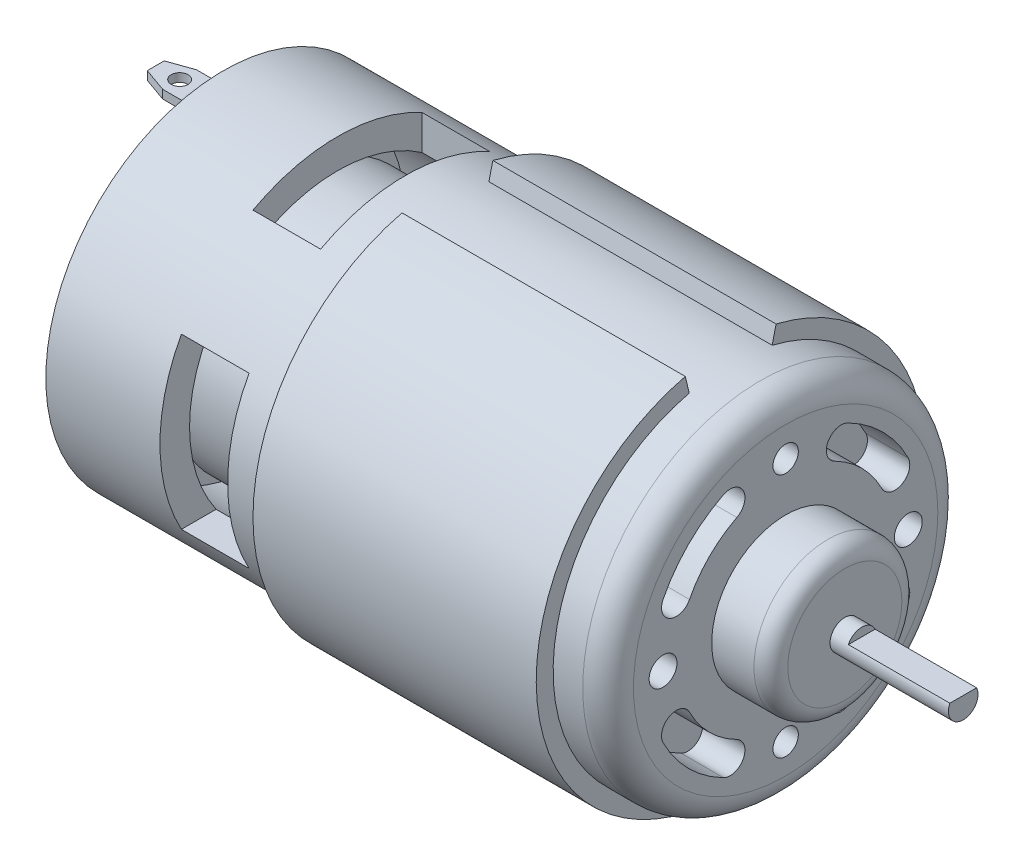
SolidWorks part; units mm, degrees
material "1060 Alloy"
ref_plane "Front Plane" through (0, 0, 0) normal (0, 0, 1) x (1, 0, 0)
ref_plane "Top Plane" through (0, 0, 0) normal (0, 1, 0) x (1, 0, 0)
ref_plane "Right Plane" through (0, 0, 0) normal (1, 0, 0) x (0, 0, -1)
sketch "Sketch1" plane through (0, 0, 0) normal (1, 0, 0) x (0, 0, -1)
  circle A0 centre (0, 0) radius 21
  dimension "D1" = 42
extrude "Boss-Extrude1" add sketch "Sketch1" along normal blind 66.5
fillet "Fillet1" radius 3 1 edges at (66.5, 0, -21)
sketch "Sketch2" plane through (66.5, 0, 0) normal (1, 0, 0) x (0, 0, -1)
  circle A0 centre (0, 0) radius 8.75
  dimension "D1" = 17.5
extrude "Boss-Extrude2" add sketch "Sketch2" along normal blind 7
fillet "Fillet2" radius 2 1 edges at (73.5, 0, -8.75)
sketch "Sketch3" plane through (73.5, 0, 0) normal (1, 0, 0) x (0, 0, -1)
  circle A0 centre (0, 0) radius 1.75
  dimension "D1" = 3.5
extrude "Boss-Extrude3" add sketch "Sketch3" along normal blind 14
ref_plane "Plane1" through (60, 0, 0) normal (1, 0, 0) x (0, 0, -1)
sketch "Sketch4" plane through (60, 0, 0) normal (1, 0, 0) x (0, 0, -1)
  line L0 (-5.3694, 22.3645) -> (-4.9025, 20.4197)
  line L1 (4.9025, 20.4197) -> (5.4896, 22.8652)
  circle A0 centre (0, 0) radius 23
  circle A1 centre (0, 0) radius 21 construction
  circle A2 centre (0, 0) radius 21
  dimension "D1" = 46
  dimension "D2" = 42
extrude "Boss-Extrude4" add sketch "Sketch4" against normal blind 33.5 contours A2 L0 A0 L1 region at (60, 21.2413, 5.7642)
sketch "Sketch5" plane through (0, 0, 0) normal (-1, 0, 0) x (0, 0, 1)
  line L0 (0, 21) -> (0, -21) construction
  line L2 (-2, 17.5) -> (2, 17.5)
  line L3 (-2, 17.5) -> (-2, 16.5)
  line L4 (-2, 16.5) -> (2, 16.5)
  line L5 (2, 17.5) -> (2, 16.5)
  line L6 (-2, 17.5) -> (2, 16.5) construction
  line L7 (-2, 16.5) -> (2, 17.5) construction
  line L8 (-2, -16.5) -> (2, -16.5)
  line L9 (-2, -16.5) -> (-2, -17.5)
  line L10 (-2, -17.5) -> (2, -17.5)
  line L11 (2, -16.5) -> (2, -17.5)
  line L12 (-2, -16.5) -> (2, -17.5) construction
  line L13 (-2, -17.5) -> (2, -16.5) construction
  circle A0 centre (0, 0) radius 21 construction
  arc A1 (-4.9025, 20.4197) -> (4.9025, 20.4197) centre (0, 0) ccw construction
  circle A2 centre (0, 0) radius 19
  point P7 (0, 17)
  point P12 (0, -17)
  dimension "D5" = 2
  dimension "D1" = 34
  dimension "D2" = 17
  dimension "D3" = 4
  dimension "D4" = 1
extrude "Cut-Extrude1" cut sketch "Sketch5" against normal blind 2
extrude "Boss-Extrude5" add sketch "Sketch5<3>" along normal blind 8 contours L4 L5 L2 L3 | L8 L11 L10 L9
sketch "Sketch5<3>" plane through (0, 0, 0) normal (-1, 0, 0) x (0, 0, 1) same geometry as "Sketch5"
sketch "Sketch6" plane through (0, -17.5, 0) normal (0, -1, 0) x (1, 0, 0)
  line L0 (-5.1716, -2) -> (-8, -1)
  line L1 (2, -2) -> (-8, -2) construction
  line L2 (-8, -2) -> (-8, 2) construction
  line L3 (-8, -1) -> (-8, 1)
  line L4 (-8, 1) -> (-5.1716, 2)
  line L5 (2, 2) -> (-8, 2) construction
  line L6 (-5.1716, -2) -> (-8, -2)
  line L7 (-8, -2) -> (-8, -1)
  line L8 (-7.7692, 1.1937) -> (-8, 1)
  line L9 (-8, 1) -> (-8, 2)
  line L10 (-8, 2) -> (-5.1716, 2)
  line M7 (2, 2) -> (-8, 2)
  line M8 (-8, 2) -> (-8, -2)
  line M9 (-8, -2) -> (2, -2)
  dimension "D1" = 3
  dimension "D2" = 1
extrude "Cut-Extrude2" cut sketch "Sketch6" against normal blind 37 contours L0 M9 M8 | L4 M8 M7 region at (-7.0572, -17.5, -1.6667) region at (-7.0572, -17.5, 1.6667)
ref_plane "Plane2" through (0, 21, 0) normal (0, 1, 0) x (1, 0, 0)
sketch "Sketch7" plane through (0, 21, 0) normal (0, 1, 0) x (1, 0, 0)
  line L0 (0, 0) -> (29.2331, 0) construction
  line L1 (21.5, -21) -> (21.5, 21) construction
  line L2 (0, -21) -> (26.5, -21) construction
  line L3 (26.5, 21) -> (0, 21) construction
  line L4 (26.5, 23) -> (26.5, -23) construction
  line L6 (21.5, -10) -> (13.5, -10)
  line L7 (21.5, -10) -> (21.5, 10)
  line L8 (21.5, 10) -> (13.5, 10)
  line L9 (13.5, -10) -> (13.5, 10)
  dimension "D1" = 5
  dimension "D2" = 10
  dimension "D3" = 10
  dimension "D4" = 8
extrude "Cut-Extrude3" cut sketch "Sketch7" against normal through all
pattern_circular "CirPattern1" count 2 every 90 about axis through (0, 0, 0) along (-1, 0, 0) of "Cut-Extrude3"
sketch "Sketch9" plane through (2, 0, 0) normal (-1, 0, 0) x (0, 0, 1)
  circle A0 centre (0, 0) radius 17.5
  dimension "D1" = 35
extrude "Boss-Extrude6" add sketch "Sketch9" against normal up to surface (64.5 mm away) up to face at (66.5, 0, -8.75)
sketch "Sketch10" plane through (0, 17.5, 0) normal (0, 1, 0) x (1, 0, 0)
  line L0 (-8, 0) -> (0, 0) construction
  line L1 (-8, 1) -> (-8, -1) construction
  line L2 (-5.1716, 2) -> (-5.1716, -2) construction
  line L3 (-8, 1) -> (-5.1716, 2) construction
  line L4 (2, 2) -> (-5.1716, 2) construction
  circle A0 centre (-5.1716, 0) radius 1
  dimension "D1" = 2
extrude "Cut-Extrude4" cut sketch "Sketch10" against normal through all and the other way through all
sketch "Sketch11" plane through (66.5, 0, 0) normal (1, 0, 0) x (0, 0, -1)
  line L0 (18, 0) -> (-18, 0) construction
  line L1 (0, 14.5) -> (0, -14.5) construction
  line L2 (-6.5648, 12.9288) -> (0, 14.5)
  line L3 (-12.9288, 6.5648) -> (-14.5, 0)
  circle A0 centre (0, 0) radius 14.5
  circle A1 centre (0, 0) radius 18 construction
  circle A2 centre (0, -14.5) radius 1.5
  circle A3 centre (0, 14.5) radius 1.5
  arc A4 (-12.9288, 6.5648) -> (-6.5648, 12.9288) centre (0, 0) cw construction
  arc A5 (-7.3571, 14.4891) -> (-14.4891, 7.3571) centre (0, 0) ccw
  arc A6 (-5.7725, 11.3684) -> (-11.3684, 5.7725) centre (0, 0) ccw
  arc A7 (-5.7725, 11.3684) -> (-7.3571, 14.4891) centre (-6.5648, 12.9288) ccw
  arc A8 (-14.4891, 7.3571) -> (-11.3684, 5.7725) centre (-12.9288, 6.5648) ccw
  arc A9 (6.5648, 12.9288) -> (12.9288, 6.5648) centre (0, 0) cw construction
  arc A10 (14.4891, 7.3571) -> (7.3571, 14.4891) centre (0, 0) ccw
  arc A11 (11.3684, 5.7725) -> (5.7725, 11.3684) centre (0, 0) ccw
  arc A12 (11.3684, 5.7725) -> (14.4891, 7.3571) centre (12.9288, 6.5648) ccw
  arc A13 (7.3571, 14.4891) -> (5.7725, 11.3684) centre (6.5648, 12.9288) ccw
  arc A14 (12.9288, -6.5648) -> (6.5648, -12.9288) centre (0, 0) cw construction
  arc A15 (7.3571, -14.4891) -> (14.4891, -7.3571) centre (0, 0) ccw
  arc A16 (5.7725, -11.3684) -> (11.3684, -5.7725) centre (0, 0) ccw
  arc A17 (5.7725, -11.3684) -> (7.3571, -14.4891) centre (6.5648, -12.9288) ccw
  arc A18 (14.4891, -7.3571) -> (11.3684, -5.7725) centre (12.9288, -6.5648) ccw
  arc A19 (-6.5648, -12.9288) -> (-12.9288, -6.5648) centre (0, 0) cw construction
  arc A20 (-14.4891, -7.3571) -> (-7.3571, -14.4891) centre (0, 0) ccw
  arc A21 (-11.3684, -5.7725) -> (-5.7725, -11.3684) centre (0, 0) ccw
  arc A22 (-11.3684, -5.7725) -> (-14.4891, -7.3571) centre (-12.9288, -6.5648) ccw
  arc A23 (-7.3571, -14.4891) -> (-5.7725, -11.3684) centre (-6.5648, -12.9288) ccw
  point P15 (-10.253, 10.253)
  point P28 (10.253, 10.253)
  point P35 (10.253, -10.253)
  point P42 (-10.253, -10.253)
  dimension "D1" = 29
  dimension "D2" = 3
  dimension "D3" = 3
  dimension "D4" = 3.5
  dimension "D5" = 9
  dimension "D6" = 4
hole_wizard "M4 Tapped Hole1" positions "3DSketch1" profile "Sketch12" tap size "M4" standard "KS"
sketch3d "3DSketch1"
  line L0 (66.5, 0, -18) -> (66.5, 0, 18) construction
  circle A0 centre (66.5, 0, 0) radius 14.5 construction
  point P0 (66.5, 0, 14.5)
  point P4 (81, 0, 0)
  point P7 (66.5, 0, -14.5)
cosmetic thread "Hole Thread1" parameters "D1"=8, "D2"=4
cosmetic thread "Hole Thread2" parameters "D1"=8, "D2"=4
sketch "Sketch12" plane through (66.5, 0, 14.5) normal (0, 1, 0) x (0, 0, -1)
  line L0 (0, 0) -> (0, 11.0914)
  line L1 (0, 11.0914) -> (1.65, 10.1)
  line L2 (1.65, 10.1) -> (1.65, 0)
  line L5 (1.65, 0) -> (0, 0)
  line L10 (0, 11.0914) -> (-1.65, 10.1) construction
  line L11 (0, -6.35) -> (0, 107.95) construction
  dimension "Tap Drill Dia." = 3.3
  dimension "Tap Drill Depth" = 10.1
  dimension "Drill Angle" = 118
extrude "Cut-Extrude6" cut sketch "Sketch11" against normal blind 5 contours L3 A8 A6 A7 L2 A0 | A20 A23 A0 A22 | A0 A23 A21 A22 | A0 A2 | A0 A2 | A0 A18 A16 A17 | A15 A18 A0 A17 | A0 A13 A11 A12 | A10 A13 A0 A12 | L2 A3 A0 | A0 A3 L2 | A0 A3 | L2 A7 A0 | A0 A8 L3 | A6 A8 A5 A7 region at (66.5, 13.2966, 5.4913) region at (66.5, 9.3901, 9.3901) region at (66.5, 5.4913, 13.2966) region at (66.5, 14.367, 0.9678) region at (66.5, 13.8135, -0.0675) region at (66.5, 15.1224, 0) region at (66.5, 10.5604, -10.5604) region at (66.5, 9.3902, -9.3902) region at (66.5, -9.3902, 9.3902) region at (66.5, -10.5604, 10.5604) region at (66.5, -13.8496, 0) region at (66.5, -15.1224, 0) region at (66.5, -10.5604, -10.5604) region at (66.5, -9.3902, -9.3902)
sketch "Sketch13" plane through (2, 0, 0) normal (-1, 0, 0) x (0, 0, 1)
  circle A0 centre (0, 0) radius 15
  dimension "D1" = 30
extrude "Boss-Extrude7" add sketch "Sketch13" along normal blind 1
chamfer "Chamfer1" distance 2 distance2 3.5 1 edges at (1, 0, 15) first distance on face at (1, 0, 15)
sketch "Sketch15" plane through (2, 0, 0) normal (-1, 0, 0) x (0, 0, 1)
  line L0 (1, 17) -> (-1, 17) construction
  line L1 (1, 17.5) -> (1, 16.5) construction
  line L2 (-1, 17.5) -> (-1, 16.5) construction
  line L3 (0, 17.5) -> (0, 16.5315) construction
  line L4 (19, 0) -> (-19, 0) construction
  line L5 (3, 19.5) -> (-3, 19.5)
  line L6 (3, 19.5) -> (3, 14.5)
  line L7 (3, 14.5) -> (-3, 14.5)
  line L8 (-3, 19.5) -> (-3, 14.5)
  line L9 (3, 19.5) -> (-3, 14.5) construction
  line L10 (3, 14.5) -> (-3, 19.5) construction
  line L11 (-3, -19.5) -> (-3, -14.5)
  line L12 (3, -19.5) -> (-3, -19.5)
  line L13 (3, -19.5) -> (3, -14.5)
  line L14 (3, -14.5) -> (-3, -14.5)
  circle A0 centre (0, 0) radius 19 construction
  circle A1 centre (0, 0) radius 19 construction
  point P10 (0, 17)
  dimension "D1" = 6
  dimension "D2" = 5
extrude "Boss-Extrude8" add sketch "Sketch15" along normal blind 1
sketch "Sketch16" plane through (2, 0, 0) normal (-1, 0, 0) x (0, 0, 1)
  line L0 (-19, 0) -> (19, 0) construction
  arc A0 (-3, 18.7617) -> (-3, -18.7617) centre (0, 0) ccw construction
chamfer "Chamfer2" distance 1 angle 32 6 edges at (1, -16.6308, -3) (1, -14.5, 0) (1, -16.6308, 3) (1, 16.6308, 3) (1, 16.6308, -3) (1, 14.5, 0) first distance on face at (1, -17, 0) first distance on face at (1, 17, 0)
sketch "Sketch17" plane through (1, 0, 0) normal (-1, 0, 0) x (0, 0, 1)
  line L0 (-19, 0) -> (19, 0) construction
  circle A0 centre (0, 0) radius 6.1849
extrude "Boss-Extrude9" add sketch "Sketch17" along normal blind 3
fillet "Fillet3" radius 1 1 edges at (-2, 0, 6.1849)
sketch "Sketch19" plane through (-2, 0, 0) normal (-1, 0, 0) x (0, 0, 1)
  circle A0 centre (0, 0) radius 2
  dimension "D1" = 4
extrude "Boss-Extrude10" add sketch "Sketch19" along normal blind 3
fillet "Fillet4" radius 1 1 edges at (-5, 0, 2)
sketch "Sketch20" plane through (1, 0, 0) normal (-1, 0, 0) x (0, 0, 1)
  line L0 (-9, 0) -> (9, 0) construction
  line L1 (0, 0) -> (6.364, -6.364) construction
  line L2 (0, 11.5) -> (0, -11.5) construction
  line L3 (0, 0) -> (-6.364, 6.364) construction
  circle A0 centre (0, 0) radius 9
  circle A1 centre (0, 0) radius 11.5 construction
  arc A2 (4.1002, 8.0118) -> (8.0118, 4.1002) centre (0, 0) cw construction
  arc A3 (-8.0118, 4.1002) -> (-4.1002, 8.0118) centre (0, 0) cw construction
  arc A4 (-4.6696, 9.1245) -> (-9.1245, 4.6696) centre (0, 0) ccw
  arc A5 (-3.5307, 6.899) -> (-6.899, 3.5307) centre (0, 0) ccw
  arc A6 (-3.5307, 6.899) -> (-4.6696, 9.1245) centre (-4.1002, 8.0118) ccw
  arc A7 (-9.1245, 4.6696) -> (-6.899, 3.5307) centre (-8.0118, 4.1002) ccw
  arc A8 (9.1245, 4.6696) -> (4.6696, 9.1245) centre (0, 0) ccw
  arc A9 (6.899, 3.5307) -> (3.5307, 6.899) centre (0, 0) ccw
  arc A10 (6.899, 3.5307) -> (9.1245, 4.6696) centre (8.0118, 4.1002) ccw
  arc A11 (4.6696, 9.1245) -> (3.5307, 6.899) centre (4.1002, 8.0118) ccw
  arc A12 (8.0118, -4.1002) -> (4.1002, -8.0118) centre (0, 0) cw construction
  arc A13 (4.6696, -9.1245) -> (9.1245, -4.6696) centre (0, 0) ccw
  arc A14 (3.5307, -6.899) -> (6.899, -3.5307) centre (0, 0) ccw
  arc A15 (3.5307, -6.899) -> (4.6696, -9.1245) centre (4.1002, -8.0118) ccw
  arc A16 (9.1245, -4.6696) -> (6.899, -3.5307) centre (8.0118, -4.1002) ccw
  arc A17 (-4.1002, -8.0118) -> (-8.0118, -4.1002) centre (0, 0) cw construction
  arc A18 (-9.1245, -4.6696) -> (-4.6696, -9.1245) centre (0, 0) ccw
  arc A19 (-6.899, -3.5307) -> (-3.5307, -6.899) centre (0, 0) ccw
  arc A20 (-6.899, -3.5307) -> (-9.1245, -4.6696) centre (-8.0118, -4.1002) ccw
  arc A21 (-4.6696, -9.1245) -> (-3.5307, -6.899) centre (-4.1002, -8.0118) ccw
  point P8 (-6.364, 6.364)
  point P24 (6.364, 6.364)
  point P32 (6.364, -6.364)
  point P39 (-6.364, -6.364)
  dimension "D1" = 2.5
  dimension "D2" = 2.5
  dimension "D3" = 2.8
  dimension "D4" = 45
  dimension "D5" = 4
extrude "Cut-Extrude7" cut sketch "Sketch20" against normal blind 5 contours A0 A21 A19 A20 | A18 A21 A0 A20 | A0 A7 A5 A6 | A4 A7 A0 A6 | A0 A11 A9 A10 | A8 A11 A0 A10 | A0 A16 A14 A15 | A13 A16 A0 A15 region at (1, 5.7673, 5.7673) region at (1, 6.5993, 6.5993) region at (1, -6.5993, 6.5993) region at (1, -5.7673, 5.7673) region at (1, 5.7673, -5.7673) region at (1, 6.5993, -6.5993) region at (1, -6.5993, -6.5993) region at (1, -5.7673, -5.7673)
ref_plane "Plane4" through (30, 0, 0) normal (1, 0, 0) x (0, 0, -1)
sketch "Sketch22" plane through (30, 0, 0) normal (1, 0, 0) x (0, 0, -1)
  circle A0 centre (0, 0) radius 15
  circle A1 centre (0, 0) radius 17.5
  dimension "D1" = 35
  dimension "D2" = 30
extrude "Cut-Extrude8" cut sketch "Sketch22" against normal blind 26
ref_plane "Plane5" through (4, 0, 0) normal (1, 0, 0) x (0, 0, -1)
sketch "Sketch23" plane through (4, 0, 0) normal (1, 0, 0) x (0, 0, -1)
  circle A0 centre (0, 0) radius 17.5
  circle A1 centre (0, 0) radius 6
  dimension "D1" = 35
  dimension "D2" = 12
extrude "Cut-Extrude9" cut sketch "Sketch23" along normal blind 5
sketch "Sketch24" plane through (87.5, 0, 0) normal (1, 0, 0) x (0, 0, -1)
  line L0 (0, 1.75) -> (0, 0.75) construction
  line L1 (0, 0.75) -> (-1.5811, 0.75)
  line L2 (-1.5811, 0.75) -> (1.5811, 0.75)
  circle A0 centre (0, 0) radius 1.75 construction
  circle A1 centre (0, 0) radius 1.75 construction
  arc A2 (1.5811, 0.75) -> (-1.5811, 0.75) centre (0, 0) ccw
  circle M3 centre (0, 0) radius 1.75
extrude "Cut-Extrude10" cut sketch "Sketch24" against normal blind 12 contours L0 A2 L1 | L0 L2 M3 region at (87.5, 1.1618, -0.6246) region at (87.5, 1.1618, 0.6246)
